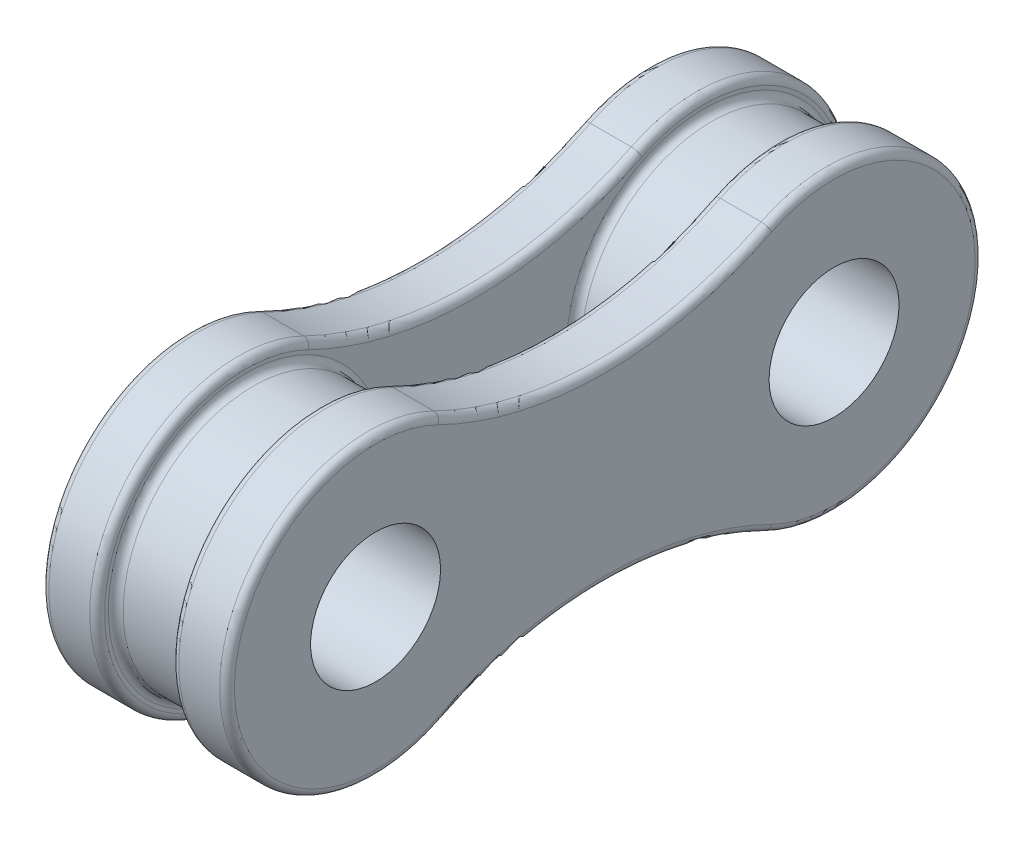
SolidWorks part; units mm, degrees
ref_plane "Alzado" through (0, 0, 0) normal (0, 0, 1) x (1, 0, 0)
ref_plane "Planta" through (0, 0, 0) normal (0, 1, 0) x (1, 0, 0)
ref_plane "Vista lateral" through (0, 0, 0) normal (1, 0, 0) x (0, 0, -1)
sketch "Croquis1" plane through (0, 0, 0) normal (1, 0, 0) x (0, 0, -1)
  line L0 (-6.175, 0) -> (6.175, 0) construction
  line L1 (0, 3.438) -> (0, -3.438) construction
  circle A0 centre (-6.175, 0) radius 1.75
  arc A1 (-4.4107, 3.5899) -> (-4.4107, -3.5899) centre (-6.175, 0) ccw
  circle A2 centre (6.175, 0) radius 1.75
  arc A3 (4.4107, 3.5899) -> (4.4107, -3.5899) centre (6.175, 0) cw
  arc A4 (-4.4107, 3.5899) -> (4.4107, 3.5899) centre (0, 12.5646) ccw
  arc A5 (-4.4107, -3.5899) -> (4.4107, -3.5899) centre (0, -12.5646) cw
  point P4 (0, 0)
  point P8 (0, 0)
  dimension "D2" = 8
  dimension "D3" = 3.5
  dimension "D4" = 10
  dimension "D1" = 12.35
extrude "Saliente-Extruir1" add sketch "Croquis1" along normal blind 1.5 from offset 1
sketch "Croquis2" plane through (0, 0, 0) normal (1, 0, 0) x (0, 0, -1)
  circle A0 centre (6.175, 0) radius 1.75 construction
  circle A1 centre (-6.175, 0) radius 1.75 construction
  circle A2 centre (6.175, 0) radius 1.75
  circle A3 centre (-6.175, 0) radius 1.75
  arc A4 (-4.4107, 3.5899) -> (4.4107, 3.5899) centre (0, 12.5646) ccw
  arc A5 (-4.4107, 3.5899) -> (-4.4107, -3.5899) centre (-6.175, 0) ccw
  arc A6 (4.4107, -3.5899) -> (-4.4107, -3.5899) centre (0, -12.5646) ccw
  arc A7 (4.4107, -3.5899) -> (4.4107, 3.5899) centre (6.175, 0) ccw
  arc A8 (-4.4107, 3.5899) -> (4.4107, 3.5899) centre (0, 12.5646) ccw
  arc A9 (-4.4107, 3.5899) -> (-4.4107, -3.5899) centre (-6.175, 0) ccw
  arc A10 (4.4107, -3.5899) -> (-4.4107, -3.5899) centre (0, -12.5646) ccw
  arc A11 (4.4107, -3.5899) -> (4.4107, 3.5899) centre (6.175, 0) ccw
  dimension "D1" = 0
extrude "Saliente-Extruir2" add sketch "Croquis2" against normal blind 1.5 from offset 1 separate body offset against normal yes
sketch "Croquis3" plane through (0, 0, 0) normal (1, 0, 0) x (0, 0, -1)
  circle A0 centre (6.175, 0) radius 1.75 construction
  circle A1 centre (-6.175, 0) radius 1.75 construction
  circle A2 centre (6.175, 0) radius 1.75
  circle A3 centre (-6.175, 0) radius 1.75
  circle A4 centre (-6.175, 0) radius 3.5
  circle A5 centre (6.175, 0) radius 3.5
  dimension "D1" = 7
extrude "Saliente-Extruir3" add sketch "Croquis3" along normal up to next (1 mm away) and the other way up to next (1 mm away)
fillet "Redondeo1" radius 0.2 22 edges at (2.5, 0, -10.175) (2.5, -2.5646, 0) (2.5, 0, 10.175) (1, 0, 10.175) (1, -2.5646, 0) (1, 0, -10.175) (1, 2.5646, 0) (1, 0, -9.675) (1, 0, 2.675) (-1, 2.5646, 0) (-1, 0, -10.175) (-1, -2.5646, 0) (-1, 0, 10.175) (-1, 0, -9.675) (-1, 0, 2.675) (-2.5, -2.5646, 0) (-2.5, 0, -10.175) (-2.5, 2.5646, 0) (-2.5, 0, 10.175) (-2.5, 0, -7.925) (-2.5, 0, 4.425) (2.5, 2.5646, 0)
